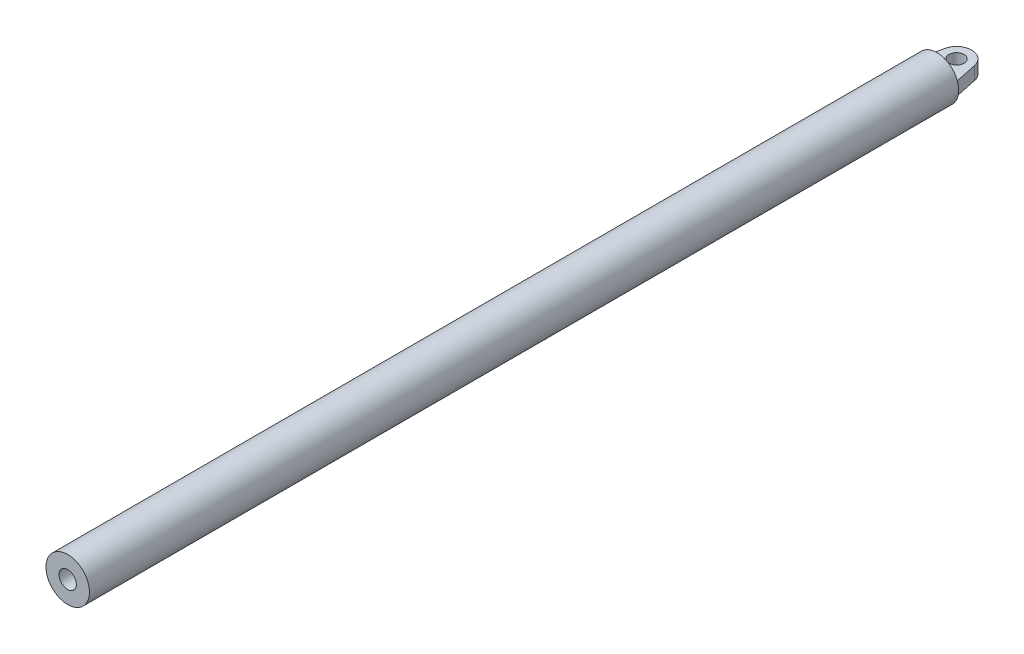
SolidWorks part; units mm, degrees
ref_plane "Front Plane" through (0, 0, 0) normal (0, 0, 1) x (1, 0, 0)
ref_plane "Top Plane" through (0, 0, 0) normal (0, 1, 0) x (1, 0, 0)
ref_plane "Right Plane" through (0, 0, 0) normal (1, 0, 0) x (0, 0, -1)
sketch "Sketch1" plane through (0, 0, 0) normal (0, 0, 1) x (1, 0, 0)
  circle A0 centre (0, 0) radius 50
  dimension "D1" = 100
extrude "Boss-Extrude1" add sketch "Sketch1" along normal blind 2000
sketch "Sketch2" plane through (0, 0, 0) normal (0, 1, 0) x (1, 0, 0)
  line L0 (-45, 0) -> (-34.2808, 52.0586)
  line L1 (50, 0) -> (-50, 0) construction
  line L2 (34.2808, 52.0586) -> (45, 0)
  line L3 (-45, 0) -> (45, 0)
  circle A0 centre (0, 45) radius 17.5
  arc A1 (-34.2808, 52.0586) -> (34.2808, 52.0586) centre (0, 45) cw
  dimension "D1" = 35
  dimension "D2" = 35
  dimension "D3" = 45
  dimension "D4" = 45
extrude "Boss-Extrude2" add sketch "Sketch2" along normal mid plane 30
shell "Shell1" thickness 30 removed face at (50, 0, 2000)
